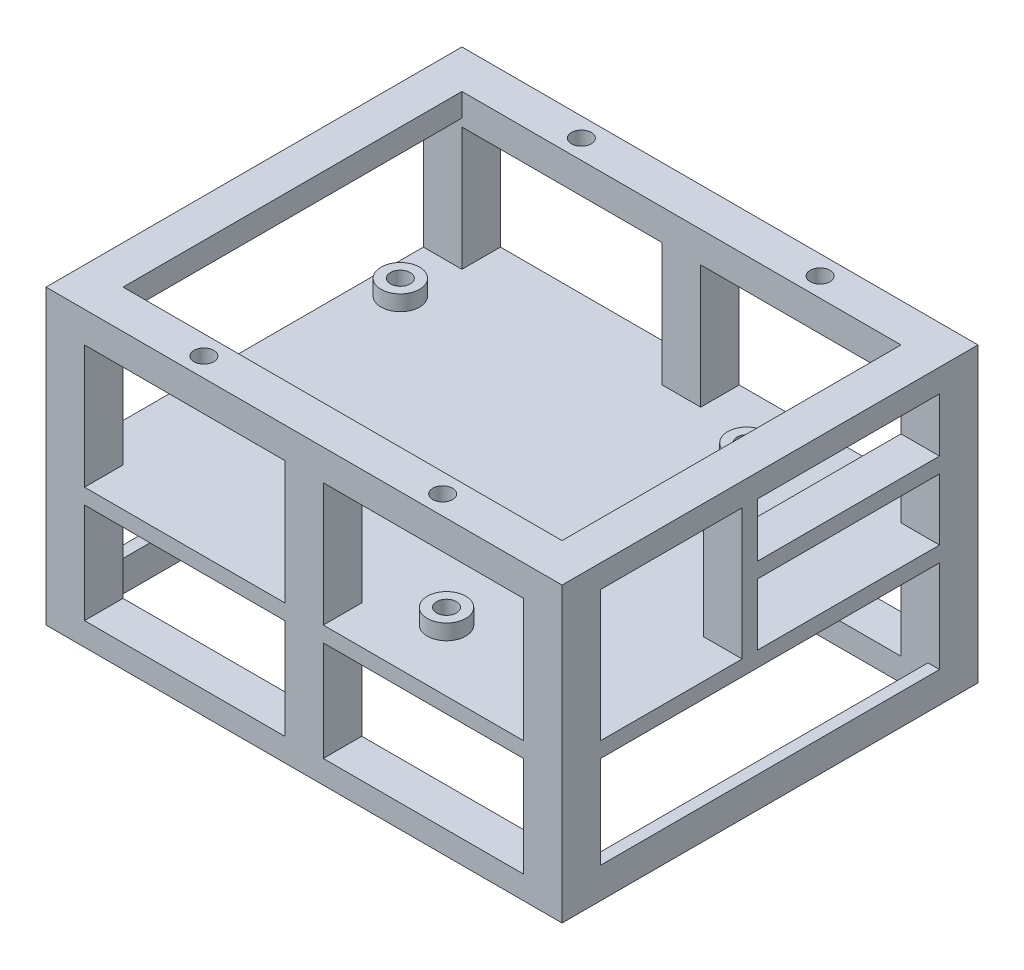
SolidWorks part; units mm, degrees
material "ABS"
ref_plane "Front Plane" through (0, 0, 0) normal (0, 0, 1) x (1, 0, 0)
ref_plane "Top Plane" through (0, 0, 0) normal (0, 1, 0) x (1, 0, 0)
ref_plane "Right Plane" through (0, 0, 0) normal (1, 0, 0) x (0, 0, -1)
sketch "Sketch1" plane through (0, 0, 0) normal (0, 1, 0) x (1, 0, 0)
  line L1 (0, 0) -> (85.09, 0)
  line L2 (0, 0) -> (0, 68.58)
  line L3 (0, 68.58) -> (85.09, 68.58)
  line L4 (85.09, 0) -> (85.09, 68.58)
  dimension "D1" = 68.58
  dimension "D2" = 85.09
extrude "Boss-Extrude1" add sketch "Sketch1" along normal blind 48.26
sketch "Sketch2" plane through (0, 48.26, 0) normal (0, 1, 0) x (1, 0, 0)
  line L0 (0, 68.58) -> (0, 0) construction
  line L1 (6.35, 62.23) -> (78.74, 62.23)
  line L2 (6.35, 62.23) -> (6.35, 6.35)
  line L3 (6.35, 6.35) -> (78.74, 6.35)
  line L4 (78.74, 62.23) -> (78.74, 6.35)
  line L5 (85.09, 0) -> (85.09, 68.58) construction
  line L6 (85.09, 68.58) -> (0, 68.58) construction
  line L7 (0, 0) -> (85.09, 0) construction
  dimension "D1" = 6.35
  dimension "D2" = 6.35
  dimension "D3" = 6.35
  dimension "D4" = 6.35
sketch "Sketch4" plane through (0, 0, 0) normal (-1, 0, 0) x (0, 0, 1)
  line L0 (-68.58, 48.26) -> (-68.58, 0) construction
  line L1 (-62.23, 44.45) -> (-6.35, 44.45)
  line L7 (-62.23, 22.86) -> (-6.35, 22.86)
  line L9 (-62.23, 20.32) -> (-6.35, 20.32)
  line L10 (-62.23, 20.32) -> (-62.23, 5.08)
  line L11 (-62.23, 5.08) -> (-6.35, 5.08)
  line L12 (-6.35, 20.32) -> (-6.35, 5.08)
  line L13 (-62.23, 22.86) -> (-62.23, 44.45)
  line L14 (-68.58, 0) -> (0, 0) construction
  line L15 (0, 48.26) -> (0, 0) construction
  line L16 (-6.35, 22.86) -> (-6.35, 44.45)
  dimension "D2" = 22.86
  dimension "D3" = 5.08
  dimension "D4" = 44.45
  dimension "D5" = 20.32
  dimension "D11" = 6.35
  dimension "D12" = 6.35
extrude "Cut-Extrude1" cut sketch "Sketch2" against normal blind 25.4
extrude "Cut-Extrude2" cut sketch "Sketch4" against normal through all
sketch "Sketch5" plane through (0, 0, 0) normal (0, -1, 0) x (-1, 0, 0)
  line L0 (0, 0) -> (-85.09, 0) construction
  line L1 (-83.185, 6.35) -> (-1.905, 6.35)
  line L2 (-83.185, 6.35) -> (-83.185, 62.23)
  line L3 (-83.185, 62.23) -> (-1.905, 62.23)
  line L4 (-1.905, 6.35) -> (-1.905, 62.23)
  line L5 (-85.09, 68.58) -> (0, 68.58) construction
  line L6 (0, 68.58) -> (0, 0) construction
  dimension "D1" = 81.28
  dimension "D2" = 6.35
  dimension "D3" = 1.905
  dimension "D4" = 6.35
extrude "Cut-Extrude4" cut sketch "Sketch5" against normal blind 20.32
hole_wizard "#30 (0.1285) Diameter Hole1" positions "3DSketch1" profile "Sketch6" hole size "#30" standard "ANSI Inch"
sketch3d "3DSketch1"
  line L0 (0, 48.26, 0) -> (85.09, 48.26, 0) construction
  line L1 (0, 48.26, -68.58) -> (0, 48.26, 0) construction
  line L3 (85.09, 48.26, -68.58) -> (0, 48.26, -68.58) construction
  line L4 (85.09, 48.26, 0) -> (85.09, 48.26, -68.58) construction
  line L5 (6.35, 48.26, -6.35) -> (78.74, 48.26, -6.35) construction
  point P2 (22.86, 48.26, -3.175)
  point P4 (22.86, 48.26, -65.405)
  point P30 (62.23, 48.26, -65.405)
  point P32 (62.23, 48.26, -3.175)
  dimension "D1" = 22.86
  dimension "D2" = 22.86
  dimension "D3" = 22.86
  dimension "D4" = 22.86
  dimension "D5" = 3.175
  dimension "D6" = 3.175
  dimension "D7" = 3.175
  dimension "D8" = 3.175
sketch "Sketch6" plane through (22.86, 48.26, -3.175) normal (1, 0, 0) x (0, 0, 1)
  line L0 (0, 0) -> (0, 13.6806)
  line L1 (0, 13.6806) -> (1.6319, 12.7)
  line L2 (1.6319, 12.7) -> (1.6319, 0)
  line L5 (1.6319, 0) -> (0, 0)
  line L10 (0, 13.6806) -> (-1.632, 12.7) construction
  line L11 (0, -6.35) -> (0, 107.95) construction
  dimension "Hole Dia." = 3.2639
  dimension "Hole Depth" = 12.7
  dimension "Drill Angle" = 118
sketch "Sketch9" plane through (0, 0, 0) normal (0, 0, 1) x (1, 0, 0)
  line L0 (0, 0) -> (85.09, 0) construction
  line L9 (6.35, 3.81) -> (39.37, 3.81)
  line L10 (6.35, 3.81) -> (6.35, 20.32)
  line L11 (6.35, 20.32) -> (39.37, 20.32)
  line L12 (39.37, 3.81) -> (39.37, 20.32)
  line L13 (6.35, 43.18) -> (39.37, 43.18)
  line L14 (6.35, 43.18) -> (6.35, 22.86)
  line L15 (6.35, 22.86) -> (39.37, 22.86)
  line L16 (39.37, 43.18) -> (39.37, 22.86)
  line L17 (45.72, 43.18) -> (78.74, 43.18)
  line L18 (45.72, 43.18) -> (45.72, 22.86)
  line L19 (45.72, 22.86) -> (78.74, 22.86)
  line L20 (78.74, 43.18) -> (78.74, 22.86)
  line L21 (45.72, 3.81) -> (78.74, 3.81)
  line L22 (45.72, 3.81) -> (45.72, 20.32)
  line L23 (45.72, 20.32) -> (78.74, 20.32)
  line L24 (78.74, 3.81) -> (78.74, 20.32)
  line L25 (0, 48.26) -> (0, 0) construction
  line L26 (85.09, 48.26) -> (85.09, 0) construction
  dimension "D1" = 3.81
  dimension "D2" = 20.32
  dimension "D3" = 22.86
  dimension "D4" = 43.18
  dimension "D5" = 6.35
  dimension "D6" = 6.35
  dimension "D7" = 6.35
  dimension "D8" = 6.35
extrude "Cut-Extrude5" cut sketch "Sketch9" against normal through all
sketch "Sketch10" plane through (0, 22.86, 0) normal (0, 1, 0) x (1, 0, 0)
  line L0 (39.37, 6.35) -> (45.72, 6.35) construction
  line L5 (71.12, 7.62) -> (2.54, 7.62)
  line L6 (71.12, 7.62) -> (71.12, 60.96)
  line L7 (71.12, 60.96) -> (2.54, 60.96)
  line L8 (2.54, 7.62) -> (2.54, 60.96)
  line L9 (0, 62.23) -> (0, 6.35) construction
  circle A0 centre (5.08, 53.34) radius 1.6319
  circle A1 centre (5.08, 25.4) radius 1.632
  circle A2 centre (57.15, 58.42) radius 1.6319
  circle A3 centre (55.88, 10.16) radius 1.6319
  circle A4 centre (57.15, 58.42) radius 3.175
  circle A5 centre (55.88, 10.16) radius 3.175
  circle A6 centre (5.08, 25.4) radius 3.175
  circle A7 centre (5.08, 53.34) radius 3.175
  dimension "D5" = 3.2639
  dimension "D10" = 3.2639
  dimension "D11" = 3.2639
  dimension "D14" = 3.2639
  dimension "D17" = 6.35
  dimension "D18" = 6.35
  dimension "D19" = 6.35
  dimension "D20" = 6.35
  dimension "D1" = 68.58
  dimension "D2" = 53.34
  dimension "D3" = 1.27
  dimension "D4" = 2.54
  dimension "D6" = 2.54
  dimension "D7" = 7.62
  dimension "D8" = 2.54
  dimension "D9" = 35.56
  dimension "D12" = 15.24
  dimension "D13" = 50.8
  dimension "D15" = 13.97
  dimension "D16" = 2.54
extrude "Boss-Extrude2" add sketch "Sketch10" along normal blind 2.54 contours L5 A5 A3 | L8 A6 A1 | L8 A7 A0 | L7 A4 | L8 A7 | L8 A6 | L5 A5 | A2 | A4 region at (55.88, 22.86, -7.3637) region at (55.88, 22.86, -7.7054) region at (57.15, 22.86, -61.2163) region at (2.2837, 22.86, -25.4) region at (2.6254, 22.86, -25.4) region at (6.057, 22.86, -56.271) region at (2.2837, 22.86, -53.34) region at (57.15, 22.86, -58.42)
extrude "Cut-Extrude6" cut sketch "Sketch10<3>" against normal up to next contours A2 | A3 | A1 | A0 region at (5.08, 22.86, -53.34) region at (5.08, 22.86, -25.4) region at (57.15, 22.86, -58.42) region at (55.88, 22.86, -10.16)
sketch "Sketch10<3>" plane through (0, 22.86, 0) normal (0, 1, 0) x (1, 0, 0) same geometry as "Sketch10"
sketch "Sketch12" plane through (0, 22.86, 0) normal (0, 1, 0) x (1, 0, 0)
  line L0 (85.09, 62.23) -> (85.09, 6.35) construction
  line L1 (85.09, 32.23) -> (78.74, 32.23)
  line L2 (85.09, 32.23) -> (85.09, 29.69)
  line L3 (85.09, 29.69) -> (78.74, 29.69)
  line L4 (78.74, 32.23) -> (78.74, 29.69)
  line L5 (85.09, 62.23) -> (78.74, 62.23) construction
  dimension "D1" = 30
  dimension "D2" = 2.54
  dimension "D3" = 6.35
extrude "Boss-Extrude3" add sketch "Sketch12" along normal blind 22.606
sketch "Sketch13" plane through (0, 0, -32.23) normal (0, 0, -1) x (-1, 0, 0)
  line L0 (-85.09, 44.45) -> (-85.09, 22.86) construction
  line L1 (-85.09, 33.02) -> (-78.74, 33.02)
  line L2 (-85.09, 33.02) -> (-85.09, 35.56)
  line L3 (-85.09, 35.56) -> (-78.74, 35.56)
  line L4 (-78.74, 33.02) -> (-78.74, 35.56)
  line L5 (-78.74, 44.45) -> (-78.74, 22.86) construction
  line L6 (-85.09, 22.86) -> (-78.74, 22.86) construction
  dimension "D1" = 10.16
  dimension "D2" = 12.7
extrude "Boss-Extrude4" add sketch "Sketch13" along normal blind 33.782
